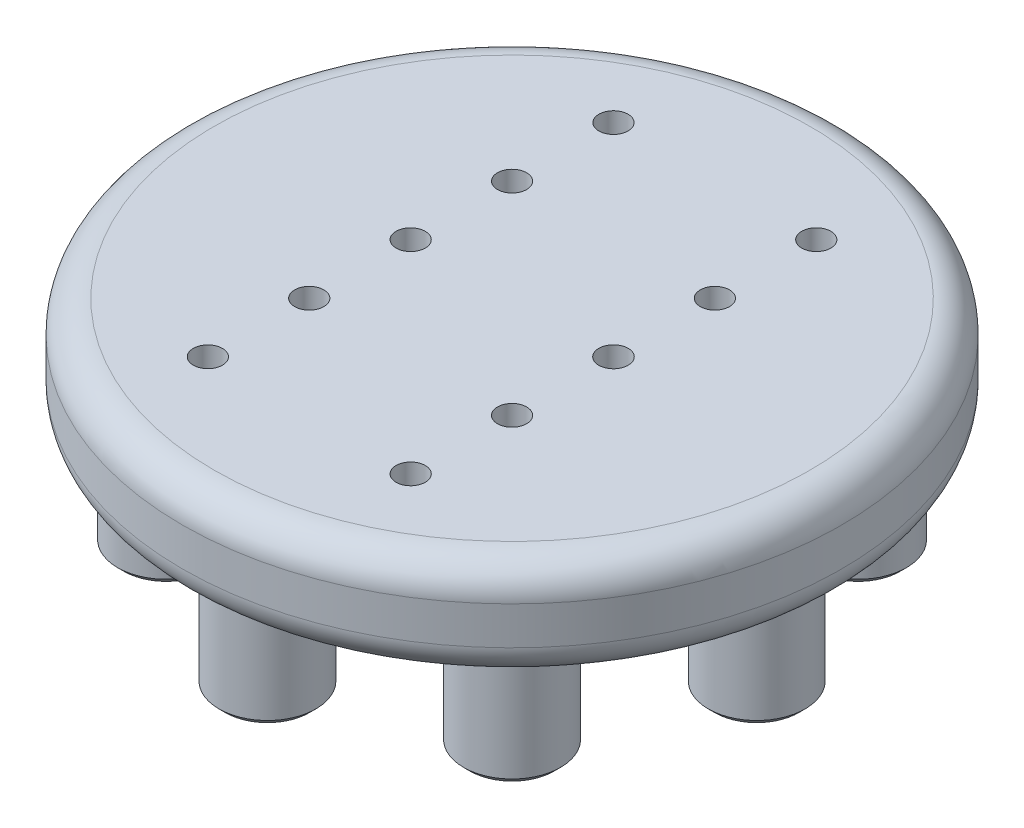
SolidWorks part; units mm, degrees
ref_plane "Front Plane" through (0, 0, 0) normal (0, 0, 1) x (1, 0, 0)
ref_plane "Top Plane" through (0, 0, 0) normal (0, 1, 0) x (1, 0, 0)
ref_plane "Right Plane" through (0, 0, 0) normal (1, 0, 0) x (0, 0, -1)
sketch "Sketch1" plane through (0, 0, 0) normal (0, 1, 0) x (1, 0, 0)
  circle A0 centre (0, 0) radius 26
  circle A1 centre (-13.6472, 13.6472) radius 3.82
  circle A2 centre (0, 19.3) radius 3.82
  circle A3 centre (13.6472, 13.6472) radius 3.82
  circle A4 centre (19.3, 0) radius 3.82
  circle A5 centre (13.6472, -13.6472) radius 3.82
  circle A6 centre (0, -19.3) radius 3.82
  circle A7 centre (-13.6472, -13.6472) radius 3.82
  circle A8 centre (-19.3, 0) radius 3.82
  circle A9 centre (0, 0) radius 6.225
  point P5 (0, 0)
  circle B0 centre (0, 19.3) radius 3.82
  circle B1 centre (13.6472, 13.6472) radius 3.82
  circle B2 centre (0, 0) radius 6.225
  circle B3 centre (-13.6472, 13.6472) radius 3.82
  circle B4 centre (-19.3, 0) radius 3.82
  circle B5 centre (-13.6472, -13.6472) radius 3.82
  circle B6 centre (0, -19.3) radius 3.82
  circle B7 centre (13.6472, -13.6472) radius 3.82
  circle B8 centre (19.3, 0) radius 3.82
sketch_block_instance "Block2-9"
sketch_block "Block2" parameters "D2"=3.9779, "D1"=8
extrude "Boss-Extrude1" add sketch "Sketch1" along normal blind 8 contours A0
sketch "Sketch2" plane through (0, 0, 0) normal (0, -1, 0) x (1, 0, 0)
  circle A1 centre (0, 0) radius 6.1
extrude "Cut-Extrude2" cut sketch "Sketch2" against normal blind 3
extrude "Boss-Extrude3" add sketch "Sketch1<11>" against normal blind 9 contours A1 | A2 | A3 | A4 | A5 | A6 | A7 | A8
sketch "Sketch1<11>" plane through (0, 0, 0) normal (0, 1, 0) x (1, 0, 0) same geometry as "Sketch1"
fillet "Fillet1" radius 2.5 2 edges at (0, 0, 26) (0, 8, 26)
sketch "Sketch3" plane through (0, 8, 0) normal (0, 1, 0) x (1, 0, 0)
  line L1 (-8, -16) -> (8, -16)
  line L2 (-8, -16) -> (-8, 16)
  line L3 (-8, 16) -> (8, 16)
  line L4 (8, -16) -> (8, 16)
  line L5 (-8, -16) -> (8, 16) construction
  line L6 (-8, 16) -> (8, -16) construction
  circle A0 centre (-8, 16) radius 1.15
  circle A1 centre (8, 16) radius 1.15
  circle A2 centre (-8, 8) radius 1.15
  circle A3 centre (8, 8) radius 1.15
  circle A4 centre (-8, -8) radius 1.15
  circle A5 centre (8, -8) radius 1.15
  circle A6 centre (-8, -16) radius 1.15
  circle A7 centre (8, -16) radius 1.15
  circle A8 centre (-8, 0) radius 1.15
  circle A9 centre (8, 0) radius 1.1602
  point P0 (0, 0)
  point P6 (-8, 8)
  point P7 (-8, 0)
  point P8 (8, 8)
  point P9 (8, 0)
  point P10 (8, -8)
  point P11 (-49.3985, 2.8418)
  point P12 (-8, -8)
  dimension "D1" = 16
  dimension "D2" = 32
extrude "Cut-Extrude3" cut sketch "Sketch3" against normal blind 6 contours A0 | A2 | A1 | A3 | A4 | A5 | A6 | A7 | A8 | A9
chamfer "Chamfer1" distance 0.5 angle 45 8 edges at (0, -9, 23.12) (13.6472, -9, 17.4672) (-13.6472, -9, 17.4672) (-19.3, -9, 3.82) (-13.6472, -9, -9.8272) (0, -9, -15.48) (13.6472, -9, -9.8272) (19.3, -9, 3.82)
